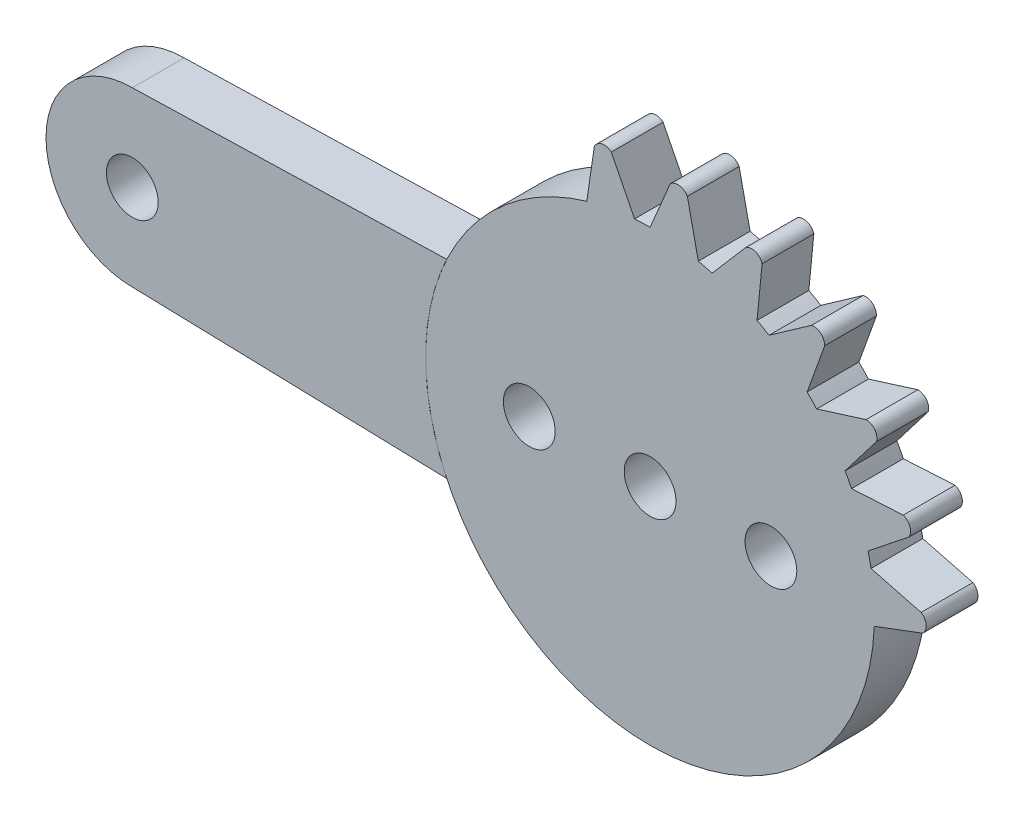
SolidWorks part; units mm, degrees
ref_plane "Piano frontale" through (0, 0, 0) normal (0, 0, 1) x (1, 0, 0)
ref_plane "Piano superiore" through (0, 0, 0) normal (0, 1, 0) x (1, 0, 0)
ref_plane "Piano destro" through (0, 0, 0) normal (1, 0, 0) x (0, 0, -1)
sketch "Schizzo1" plane through (0, 0, 0) normal (0, 0, 1) x (1, 0, 0)
  line L0 (-13, 0) -> (13, 0) construction
  circle A0 centre (0, 0) radius 13
  circle A1 centre (-7, 0) radius 1.5
  circle A2 centre (7, 0) radius 1.5
  circle A3 centre (0, 0) radius 1.5
  dimension "D1" = 26
  dimension "D4" = 3
  dimension "D5" = 3
  dimension "D6" = 3
  dimension "D2" = 7
  dimension "D3" = 7
sketch "Schizzo2" plane through (0, 0, 0) normal (0, 0, 1) x (1, 0, 0)
  line L0 (-7, 0) -> (-30, 0) construction
  line L1 (-30, 5) -> (-30, -5) construction
  line L6 (-30, 5) -> (-11.7792, 5.5)
  line L7 (-30, -5) -> (-11.7792, -5.5)
  circle A0 centre (-30, 0) radius 1.5
  arc A1 (-30, 5) -> (-30, -5) centre (-30, 0) ccw
  circle A2 centre (0, 0) radius 13 construction
  circle A3 centre (0, 0) radius 13.0045
  point P5 (-30, 5)
  point P8 (-30, -5)
  dimension "D2" = 3
  dimension "D4" = 10
  dimension "D3" = 11
  dimension "D5" = 26.009
  dimension "D1" = 23
sketch "Schizzo3" plane through (0, 0, 0) normal (0, 0, 1) x (1, 0, 0)
  line L0 (0, 13) -> (0, 0) construction
  line L1 (0, 0) -> (13, 0) construction
  line L2 (1.3976, 12.848) -> (0.8347, 12.9092) construction
  line L3 (0, -55) -> (0, 55) construction
  line L4 (1.3976, 12.848) -> (1.8006, 12.8041) construction
  line L5 (0, 13) -> (2.7952, 12.6959) construction
  line L6 (2.7952, 12.6959) -> (1.3976, 12.848) construction
  line L7 (0, 13) -> (-0.8685, 12.971) construction
  line L8 (-0.4495, 12.985) -> (-0.5424, 15.7635) construction
  line L9 (1.1676, 15.7635) -> (0, 13)
  line L10 (2.1601, 15.6279) -> (2.7952, 12.6959)
  line L11 (-3.2297, 15.4477) -> (-3.6676, 12.4798)
  line L12 (-2.2485, 15.6492) -> (-0.8989, 12.9699)
  line L13 (2.7952, 12.6959) -> (3.5952, 12.493) construction
  line L14 (3.1641, 12.6023) -> (3.1952, 12.5945) construction
  line L15 (3.1952, 12.5945) -> (3.5748, 14.0909) construction
  line L16 (5.5513, 14.7676) -> (3.5952, 12.493)
  line L17 (6.4883, 14.4136) -> (6.1973, 11.4277)
  line L18 (6.1973, 11.4277) -> (6.8885, 11.0249) construction
  line L19 (6.5429, 11.2263) -> (7.3923, 12.6837) construction
  line L20 (9.343, 12.7498) -> (6.8885, 11.0249)
  line L21 (10.1129, 12.109) -> (9.0979, 9.2859)
  line L22 (9.0979, 9.2859) -> (9.6518, 8.7087) construction
  line L23 (9.3749, 8.9973) -> (10.5474, 10.1226) construction
  line L24 (13.1229, 8.8113) -> (11.2986, 6.4297)
  line L25 (12.5142, 9.6069) -> (9.6518, 8.7087)
  line L26 (11.2986, 6.4297) -> (11.6727, 5.7226) construction
  line L27 (11.4857, 6.0762) -> (12.5229, 6.6249) construction
  line L28 (14.668, 5.8907) -> (11.6727, 5.7226)
  line L29 (14.9832, 4.9399) -> (12.6301, 3.0789)
  line L30 (12.6301, 3.0789) -> (12.7987, 2.2789) construction
  line L31 (12.7144, 2.6789) -> (14.1522, 2.9819) construction
  line L32 (15.7026, 1.5256) -> (12.7987, 2.2789)
  line L33 (15.7978, 0.5285) -> (12.9893, -0.5263)
  line L34 (-3.6676, 12.4798) -> (-0.8989, 12.9699) construction
  line L35 (-3.6676, 12.4798) -> (-0.8989, 12.9699)
  circle A0 centre (0, 0) radius 13 construction
  arc A1 (1.1676, 15.7635) -> (2.1601, 15.6279) centre (1.6117, 15.314) cw
  arc A2 (-2.2485, 15.6492) -> (-3.2297, 15.4477) centre (-2.6616, 15.1711) ccw
  arc A3 (6.4883, 14.4136) -> (5.5513, 14.7676) centre (5.8837, 14.2303) ccw
  arc A4 (9.343, 12.7498) -> (10.1129, 12.109) centre (9.4815, 12.1334) cw
  arc A5 (13.1229, 8.8113) -> (12.5142, 9.6069) centre (12.5126, 8.975) ccw
  arc A6 (14.668, 5.8907) -> (14.9832, 4.9399) centre (14.46, 5.2941) cw
  arc A7 (15.7978, 0.5285) -> (15.7026, 1.5256) centre (15.3667, 0.9904) ccw
  circle A8 centre (0, 0) radius 13
  point P13 (2.7952, 12.6959)
  dimension "D8" = 0.8685
  dimension "D18" = 3
  dimension "D20" = 26
  dimension "D15" = 0.6318
  dimension "D1" = 2.4753
  dimension "D2" = 1.0017
  dimension "D3" = 2.8732
  dimension "D4" = 3
  dimension "D5" = 3
  dimension "D6" = 2.8117
  dimension "D7" = 2.82
  dimension "D9" = 0.8
  dimension "D10" = 0.8
  dimension "D11" = 0.8253
  dimension "D12" = 0.8
  dimension "D13" = 0.8
  dimension "D14" = 0.8
  dimension "D16" = 3
  dimension "D17" = 2.7229
  dimension "D19" = 2.8418
extrude "Estrusione-Estrusione1" add sketch "Schizzo1" along normal blind 3
extrude "Estrusione-Estrusione2" add sketch "Schizzo2" along normal blind 3 contours A3 L6 A1 L7 A0 region at (-22.8827, 0, 0)
extrude "Estrusione-Estrusione3" add sketch "Schizzo3" along normal blind 3 contours A8 L35 L12 A2 L11 | A8 L10 A1 L9 | A8 L17 A3 L16 | A8 L21 A4 L20 | A8 L24 A5 L25 | A8 L29 A6 L28 | A8 L33 A7 L32 region at (1.5155, 14.1322, 0) region at (-2.487, 13.9955, 0) region at (5.4048, 13.1455, 0) region at (14.1819, 0.9422, 0) region at (8.7737, 11.182, 0) region at (11.533, 8.3069, 0) region at (13.3564, 4.8602, 0)
